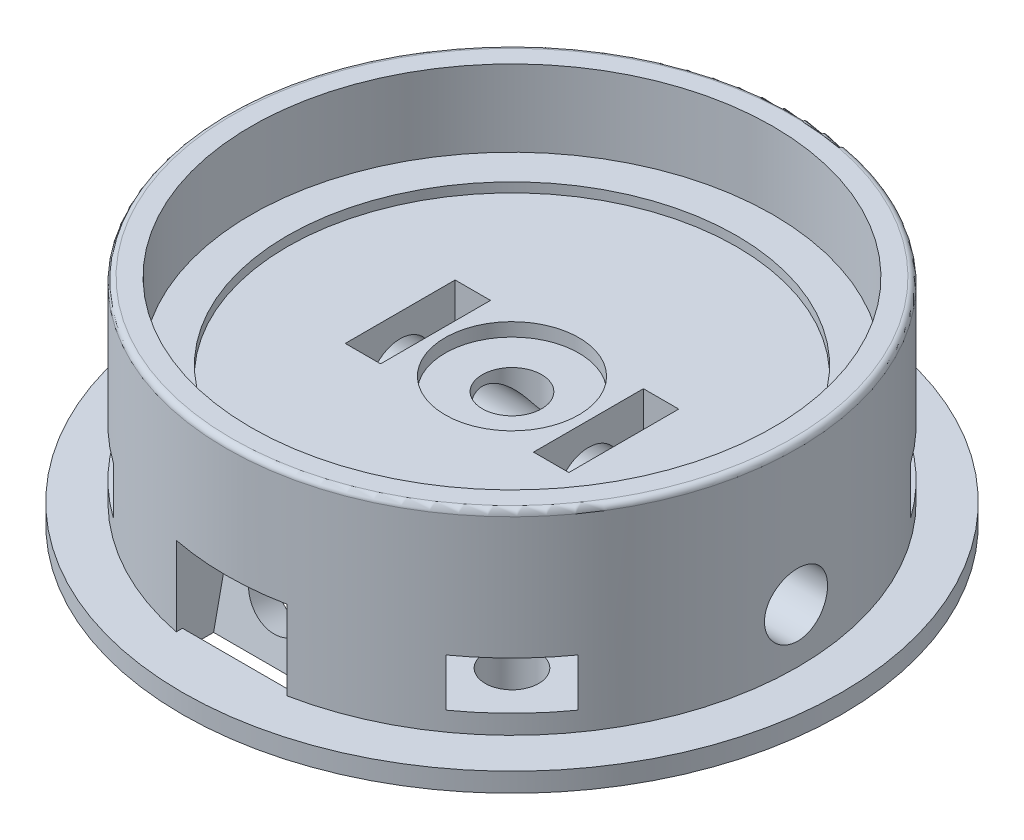
SolidWorks part; units mm, degrees
ref_plane "Front Plane" through (0, 0, 0) normal (0, 0, 1) x (1, 0, 0)
ref_plane "Top Plane" through (0, 0, 0) normal (0, 1, 0) x (1, 0, 0)
ref_plane "Right Plane" through (0, 0, 0) normal (1, 0, 0) x (0, 0, -1)
sketch "Sketch1" plane through (0, 0, 0) normal (0, 1, 0) x (1, 0, 0)
  circle A0 centre (0, 0) radius 14.95
  dimension "D1" = 29.9
extrude "Boss-Extrude1" add sketch "Sketch1" along normal blind 6.2
sketch "Sketch2" plane through (0, 6.2, 0) normal (0, 1, 0) x (1, 0, 0)
  circle A0 centre (0, 0) radius 11.75
  dimension "D1" = 23.5
extrude "Cut-Extrude1" cut sketch "Sketch2" against normal blind 0.5
sketch "Sketch3" plane through (0, 6.2, 0) normal (0, 1, 0) x (1, 0, 0)
  circle A0 centre (0, 0) radius 13.65
  circle A1 centre (0, 0) radius 14.95
  circle A2 centre (0, 0) radius 14.95 construction
  dimension "D1" = 27.3
extrude "Boss-Extrude2" add sketch "Sketch3" along normal blind 4
fillet "Fillet1" radius 0.3 1 edges at (0, 10.2, 14.95)
sketch "Sketch4" plane through (0, 5.7, 0) normal (0, 1, 0) x (1, 0, 0)
  circle A0 centre (0, 0) radius 1.55
  dimension "D1" = 3.1
extrude "Cut-Extrude2" cut sketch "Sketch4" against normal through all
ref_plane "Plane1" through (4, 0, 0) normal (1, 0, 0) x (0, 0, -1)
sketch "Sketch5" plane through (0, 0, 0) normal (1, 0, 0) x (0, 0, -1)
  line L1 (1.55, 5.7) -> (-1.55, 5.7) construction
  line L2 (-2.875, -0.05) -> (2.875, -0.05) construction
  line L3 (-2.875, -0.05) -> (-2.875, 5.7) construction
  line L4 (-2.875, 5.7) -> (2.875, 5.7) construction
  line L5 (2.875, -0.05) -> (2.875, 5.7) construction
  line L6 (-2.875, -0.05) -> (2.875, 5.7) construction
  line L7 (-2.875, 5.7) -> (2.875, -0.05) construction
  circle A0 centre (0, 2.825) radius 1.65
  dimension "D1" = 3.3
  dimension "D2" = 5.75
extrude "Cut-Extrude3" cut sketch "Sketch5" along normal through all
sketch "Sketch6" plane through (0, 0, 0) normal (0, -1, 0) x (1, 0, 0)
  circle A0 centre (0, 0) radius 1.55 construction
  circle A1 centre (0, 0) radius 1.55
  circle A2 centre (0, 0) radius 17.25
  dimension "D1" = 34.5
extrude "Boss-Extrude3" add sketch "Sketch6" along normal blind 1
sketch "Sketch7" plane through (4, 0, 0) normal (1, 0, 0) x (0, 0, -1)
  line L7 (-2.875, 5.7) -> (2.875, 5.7)
  line L8 (-2.875, 5.7) -> (-2.875, -0.05)
  line L9 (-2.875, -0.05) -> (2.875, -0.05)
  line L10 (2.875, 5.7) -> (2.875, -0.05)
  line L11 (-2.875, 5.7) -> (2.875, -0.05) construction
  line L12 (-2.875, -0.05) -> (2.875, 5.7) construction
  point P1 (0, 2.825)
  dimension "D2" = 5.75
extrude "Cut-Extrude4" cut sketch "Sketch7" along normal blind 1.85
ref_axis "Axis1" through (0, 9.9, 0) along (0, -1, 0)
pattern_circular "CirPattern1" count 2 over 360 about axis through (0, 9.9, 0) along (0, -1, 0) of "Cut-Extrude4", "Cut-Extrude3"
ref_plane "Plane2" through (0, 0, 0) normal (0, 0, 1) x (0, -1, 0)
ref_plane "Plane3" through (0, 0, 12.5) normal (0, 0, 1) x (0, -1, 0)
sketch "Sketch11" plane through (0, 0, 12.5) normal (0, 0, 1) x (0, -1, 0)
  line L0 (0, 23.2225) -> (0, -23.2225) construction
  point P4 (0, 0)
ref_plane "Plane4" through (0, 2.5421, 11.9597) normal (0, 0.2079, 0.9781) x (-1, 0, 0)
sketch "Sketch9" plane through (0, 0.4189, 12.411) normal (0, 0.2079, 0.9781) x (0, -0.9781, 0.2079)
  line L0 (-11.8543, 0) -> (-2.1706, 0) construction
  line L2 (1.4283, 2.9) -> (-4.3717, 2.9) construction
  line L3 (1.4283, 2.9) -> (1.4283, -2.9) construction
  line L4 (1.4283, -2.9) -> (-4.3717, -2.9) construction
  line L5 (-4.3717, 2.9) -> (-4.3717, -2.9) construction
  line L6 (1.4283, 2.9) -> (-4.3717, -2.9) construction
  line L7 (1.4283, -2.9) -> (-4.3717, 2.9) construction
  line L8 (0.4283, 23.2225) -> (0.4283, -23.2225) construction
  circle A0 centre (-1.4717, 0) radius 1.65
  dimension "D2" = 3.3
  dimension "D1" = 5.8
  dimension "D3" = 1
extrude "Cut-Extrude5" cut sketch "Sketch9" along normal through all and the other way blind 2
sketch "Sketch10" plane through (0, 0, 12.5) normal (0, 0.2079, 0.9781) x (0, -0.9781, 0.2079)
  line L1 (1, 2.9) -> (-4.8, 2.9) construction
  line L2 (-4.8, 2.9) -> (-4.8, -2.9) construction
  line L3 (1, -2.9) -> (-4.8, -2.9) construction
  line L5 (1, 2.9) -> (-4.8, 2.9)
  line L6 (-4.8, 2.9) -> (-4.8, -2.9)
  line L7 (1, -2.9) -> (-4.8, -2.9)
  line L8 (1, 2.9) -> (3, 2.9)
  line L9 (3, 2.9) -> (3, -2.9)
  line L10 (3, -2.9) -> (1, -2.9)
  dimension "D1" = 2
extrude "Cut-Extrude6" cut sketch "Sketch10" along normal blind 1.8
ref_plane "Plane5" through (0, 2.2302, 10.4924) normal (0, 0.2079, 0.9781) x (-1, 0, 0)
sketch "Sketch13" plane through (0, 2.2302, 10.4924) normal (0, 0.2079, 0.9781) x (-1, 0, 0)
  line L0 (-2.4902, -0.2075) -> (-3.8756, 3.5989)
  line L1 (-3.8756, 3.5989) -> (3.8756, 3.5989)
  line L2 (3.8756, 3.5989) -> (2.4902, -0.2075)
  line L3 (0, 0.6989) -> (0, 3.5989) construction
  line L4 (-2.9, 3.5989) -> (2.9, 3.5989) construction
  circle A0 centre (0, 0.6989) radius 1.65 construction
  circle A1 centre (0, 0.6989) radius 1.65 construction
  circle A2 centre (0, 0.6989) radius 2.65 construction
  arc A3 (2.4902, -0.2075) -> (-2.4902, -0.2075) centre (0, 0.6989) cw
  dimension "D1" = 20
  dimension "D2" = 1
ref_plane "Plane6" through (0, 0, 0) normal (-1, 0, 0) x (0, -1, 0)
ref_plane "Plane7" through (0, 0, 14.95) normal (0, 0, 1) x (1, 0, 0)
sketch "Sketch14" plane through (0, 0, 0) normal (-1, 0, 0) x (0, -1, 0)
  line L0 (-3.1606, 10.2947) -> (3.2723, 0) construction
  line L3 (0.0673, 10.9808) -> (-3.1606, 10.2947) construction
  line L5 (-3.1606, 10.2947) -> (-0.9985, 0.1229) construction
  arc A0 (-3.1606, 10.2947) -> (3.2723, 0) centre (14.1981, 13.9844) ccw
  dimension "D1" = 70
sweep "Cut-Sweep1" cut profiles "Sketch13" path "Sketch14"
sketch "Sketch19" plane through (0, 0, 14.95) normal (0, 0, 1) x (1, 0, 0)
  line L0 (2.9, 5.0693) -> (-2.9, 5.0693) construction
  line L1 (2.9, 5.0693) -> (-2.9, 5.0693) construction
  line L2 (14.95, 0) -> (-14.95, 0) construction
  line L3 (2.9, 0) -> (-2.9, 0) construction
  line L4 (-2.9, 5.0693) -> (-2.9, 0) construction
  line L5 (2.9, 5.0693) -> (2.9, 0) construction
  line L6 (-2.9, 4.1501) -> (2.9, 4.1501)
  line L7 (2.9, 4.1501) -> (2.9, 0)
  line L8 (2.9, 0) -> (-2.9, 0)
  line L9 (-2.9, 0) -> (-2.9, 4.1501)
  spline S0 degree 3 poles (-0.1103, 0.7763) (0.2206, 0.7763) (0.4399, 0.8212) (0.8405, 0.99) (1.0254, 1.1159) (1.2535, 1.3495) (1.3227, 1.4364) (1.4409, 1.6192) (1.4907, 1.7158) (1.5713, 1.9192) (1.6018, 2.0256) (1.6413, 2.2393) (1.6508, 2.3478) (1.6481, 2.6782) (1.6047, 2.8939) (1.4812, 3.1989) (1.431, 3.2954) (1.313, 3.4783) (1.2443, 3.5654) (1.0179, 3.8015) (0.8351, 3.9301) (0.4362, 4.1039) (0.2169, 4.1502) (-0.1103, 4.15) (-0.221, 4.1383) (-0.434, 4.0932) (-0.5375, 4.06) (-0.8386, 3.9282) (-1.0184, 3.8015) (-1.2465, 3.5629) (-1.3137, 3.4773) (-1.4313, 3.2948) (-1.4822, 3.1968) (-1.5641, 2.9938) (-1.5952, 2.8896) (-1.6378, 2.6758) (-1.6492, 2.5653) (-1.6515, 2.2381) (-1.6108, 2.0182) (-1.4501, 1.6141) (-1.3285, 1.4262) (-1.1006, 1.193) (-1.0155, 1.1217) (-0.835, 0.9992) (-0.7396, 0.9473) (-0.5381, 0.8627) (-0.4321, 0.8302) (-0.2188, 0.7873) (-0.1103, 0.7763) (0.2206, 0.7763) (0.4399, 0.8212) knots -0.03125 -0.03125 0 0 0.0625 0.0625 0.125 0.125 0.15625 0.15625 0.1875 0.1875 0.21875 0.21875 0.25 0.25 0.3125 0.3125 0.34375 0.34375 0.375 0.375 0.4375 0.4375 0.5 0.5 0.53125 0.53125 0.5625 0.5625 0.625 0.625 0.65625 0.65625 0.6875 0.6875 0.71875 0.71875 0.75 0.75 0.8125 0.8125 0.875 0.875 0.90625 0.90625 0.9375 0.9375 0.96875 0.96875 1 1 1.0625 1.0625 1.125 only from (0, 0.7763) to (0, 0.7763) construction
  spline S1 degree 3 poles (-0.1103, 0.7763) (0.2206, 0.7763) (0.4399, 0.8212) (0.8405, 0.99) (1.0254, 1.1159) (1.2535, 1.3495) (1.3227, 1.4364) (1.4409, 1.6192) (1.4907, 1.7158) (1.5713, 1.9192) (1.6018, 2.0256) (1.6413, 2.2393) (1.6508, 2.3478) (1.6481, 2.6782) (1.6047, 2.8939) (1.4812, 3.1989) (1.431, 3.2954) (1.313, 3.4783) (1.2443, 3.5654) (1.0179, 3.8015) (0.8351, 3.9301) (0.4362, 4.1039) (0.2169, 4.1502) (-0.1103, 4.15) (-0.221, 4.1383) (-0.434, 4.0932) (-0.5375, 4.06) (-0.8386, 3.9282) (-1.0184, 3.8015) (-1.2465, 3.5629) (-1.3137, 3.4773) (-1.4313, 3.2948) (-1.4822, 3.1968) (-1.5641, 2.9938) (-1.5952, 2.8896) (-1.6378, 2.6758) (-1.6492, 2.5653) (-1.6515, 2.2381) (-1.6108, 2.0182) (-1.4501, 1.6141) (-1.3285, 1.4262) (-1.1006, 1.193) (-1.0155, 1.1217) (-0.835, 0.9992) (-0.7396, 0.9473) (-0.5381, 0.8627) (-0.4321, 0.8302) (-0.2188, 0.7873) (-0.1103, 0.7763) (0.2206, 0.7763) (0.4399, 0.8212) knots -0.03125 -0.03125 0 0 0.0625 0.0625 0.125 0.125 0.15625 0.15625 0.1875 0.1875 0.21875 0.21875 0.25 0.25 0.3125 0.3125 0.34375 0.34375 0.375 0.375 0.4375 0.4375 0.5 0.5 0.53125 0.53125 0.5625 0.5625 0.625 0.625 0.65625 0.65625 0.6875 0.6875 0.71875 0.71875 0.75 0.75 0.8125 0.8125 0.875 0.875 0.90625 0.90625 0.9375 0.9375 0.96875 0.96875 1 1 1.0625 1.0625 1.125 only from (0, 0.7763) to (0, 0.7763) construction
extrude "Cut-Extrude11" cut sketch "Sketch19" against normal up to surface (0.6098 mm away) up to face at (0, 2.0347, 13.9077)
pattern_circular "CirPattern2" count 2 over 360 about axis through (0, 9.9, 0) along (0, -1, 0) of "Cut-Extrude5", "Cut-Sweep1", "Cut-Extrude6", "Cut-Extrude11"
sketch "Sketch16" plane through (0, -1, 0) normal (0, -1, 0) x (1, 0, 0)
  line L0 (0, 0) -> (-12.1976, 12.1976) construction
  line L1 (0, 11.1539) -> (0, -11.1539) construction
  circle A0 centre (0, 0) radius 17.25 construction
  circle A1 centre (-8.5206, 8.5206) radius 1.4
  circle A2 centre (-8.5206, 8.5206) radius 2.9 construction
  circle A3 centre (0, 0) radius 14.95 construction
  dimension "D2" = 2.8
  dimension "D3" = 5.8
  dimension "D1" = 45
extrude "Cut-Extrude8" cut sketch "Sketch16" against normal blind 4.5
sketch "Sketch17" plane through (0, 3.5, 0) normal (0, -1, 0) x (1, 0, 0)
  line L1 (-10.5211, 10.5211) -> (-11.2533, 7.7884) construction
  line L2 (-11.2533, 7.7884) -> (-9.2528, 5.788)
  line L3 (-9.2528, 5.788) -> (-6.5202, 6.5202)
  line L4 (-6.5202, 6.5202) -> (-5.788, 9.2528)
  line L5 (-5.788, 9.2528) -> (-7.7884, 11.2533)
  line L6 (-7.7884, 11.2533) -> (-10.5211, 10.5211) construction
  line L7 (-7.7884, 11.2533) -> (-8.8388, 12.3037)
  line L8 (-8.8388, 12.3037) -> (-12.3037, 8.8388)
  line L9 (-12.3037, 8.8388) -> (-11.2533, 7.7884)
  line L10 (-6.5202, 6.5202) -> (-8.5206, 8.5206) construction
  circle A0 centre (-8.5206, 8.5206) radius 2.45 construction
  circle A1 centre (0, 0) radius 14.95 construction
  dimension "D1" = 4.9
extrude "Cut-Extrude9" cut sketch "Sketch17" along normal blind 2.5
pattern_circular "CirPattern3" count 4 over 360 about axis through (0, 9.9, 0) along (0, -1, 0) of "Cut-Extrude8", "Cut-Extrude9"
sketch "Sketch18" plane through (0, 5.7, 0) normal (0, 1, 0) x (1, 0, 0)
  circle A2 centre (0, 0) radius 3.5
  dimension "D1" = 7
extrude "Cut-Extrude10" cut sketch "Sketch18" against normal blind 0.7
